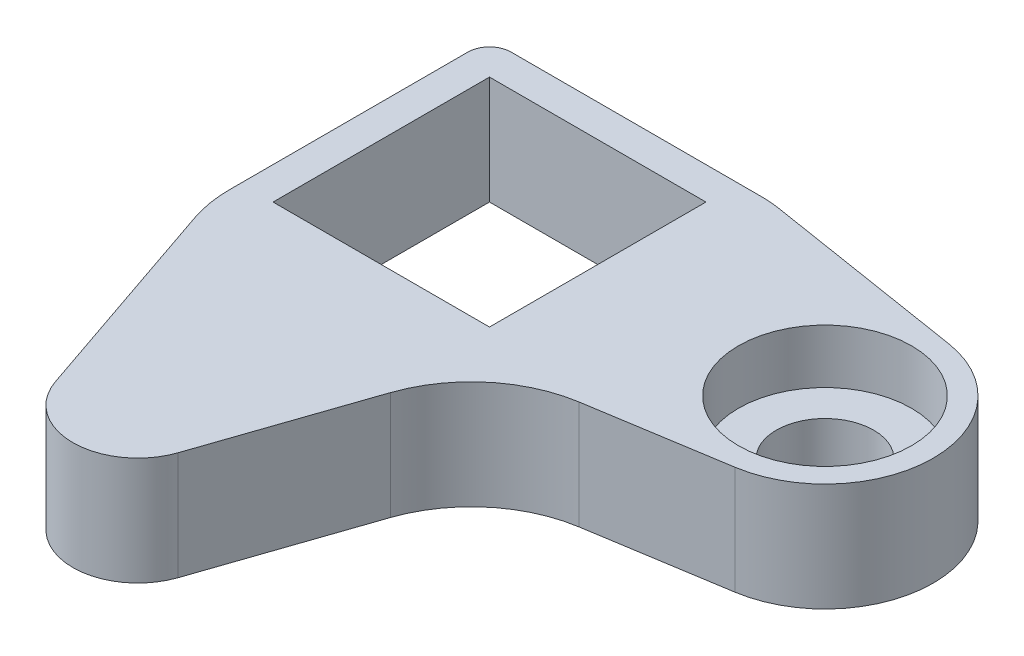
SolidWorks part; units mm, degrees
ref_plane "Front Plane" through (0, 0, 0) normal (0, 0, 1) x (1, 0, 0)
ref_plane "Top Plane" through (0, 0, 0) normal (0, 1, 0) x (1, 0, 0)
ref_plane "Right Plane" through (0, 0, 0) normal (1, 0, 0) x (0, 0, -1)
sketch "Sketch1" plane through (0, 0, 0) normal (0, 1, 0) x (1, 0, 0)
  line L0 (20, 0) -> (41, -10) construction
  line L1 (10, -42.5) -> (0, -20) construction
  line L2 (41, -10) -> (20, -20) construction
  line L3 (0, 0) -> (0, -20) construction
  line L4 (0, 0) -> (20, -20) construction
  line L5 (23.9399, 2.85) -> (42.5764, -0.125)
  line L12 (-3, -23) -> (23, -23) construction
  line L13 (0, 0) -> (20, 0) construction
  line L14 (0, 0) -> (0, -20) construction
  line L15 (0, -20) -> (20, -20) construction
  line L16 (20, 0) -> (20, -20) construction
  line L17 (10, -42.5) -> (20, -20) construction
  line L18 (-3, -21.0074) -> (-3, 1)
  line L19 (-1, 3) -> (22.0482, 3)
  line L20 (23, -23) -> (23, 3) construction
  line L21 (-3, -23) -> (23, 3) construction
  line L22 (-3, 3) -> (23, -23) construction
  line L23 (0, -20) -> (20, -20)
  line L24 (0, -20) -> (0, 0)
  line L25 (0, 0) -> (20, 0)
  line L26 (20, -20) -> (20, 0)
  line L27 (0, -20) -> (20, 0) construction
  line L28 (0, 0) -> (20, -20) construction
  line L29 (30.1306, -21.8617) -> (42.5764, -19.875)
  line L30 (20.6662, -29.8333) -> (15.678, -44.4392)
  line L31 (-2.356, -24.8857) -> (4.322, -44.4392)
  circle A4 centre (10, -42.5) radius 4 construction
  circle A5 centre (41, -10) radius 4 construction
  arc A6 (-3, 1) -> (-1, 3) centre (-1, 1) cw
  circle A7 centre (41, -10) radius 8 construction
  arc A8 (42.5764, -19.875) -> (42.5764, -0.125) centre (41, -10) ccw
  arc A9 (4.322, -44.4392) -> (15.678, -44.4392) centre (10, -42.5) ccw
  arc A10 (30.1306, -21.8617) -> (20.6662, -29.8333) centre (32.0222, -33.7117) ccw
  arc A11 (23.9399, 2.85) -> (22.0482, 3) centre (22.0482, -9) ccw
  arc A12 (-3, -21.0074) -> (-2.356, -24.8857) centre (9, -21.0074) ccw
  point P0 (10, -10)
  point P10 (10, -10)
  dimension "D6" = 8
  dimension "D7" = 16
  dimension "D8" = 20
  dimension "D9" = 12
  dimension "D10" = 12
  dimension "D11" = 12
  dimension "D5" = 2
  dimension "D2" = 20
  dimension "D3" = 3
  dimension "D4" = 42.5
  dimension "D12" = 20
  dimension "D13" = 41
extrude "Boss-Extrude1" add sketch "Sketch1" along normal blind 10
ref_plane "Plane1" through (0, 5, 0) normal (0, 1, 0) x (1, 0, 0)
sketch "Sketch2" plane through (0, 5, 0) normal (0, 1, 0) x (1, 0, 0)
  line L0 (20, 0) -> (41, -10) construction
  line L1 (10, -42.5) -> (0, -20) construction
  line L2 (41, -10) -> (20, -20) construction
  line L3 (0, 0) -> (0, -20) construction
  line L4 (0, 0) -> (20, -20) construction
  line L5 (23.9399, 2.85) -> (42.5764, -0.125) construction
  line L6 (-3, -23) -> (23, -23) construction
  line L7 (0, 0) -> (20, 0) construction
  line L8 (0, 0) -> (0, -20) construction
  line L9 (0, -20) -> (20, -20) construction
  line L10 (20, 0) -> (20, -20) construction
  line L11 (10, -42.5) -> (20, -20) construction
  line L12 (-3, -21.0074) -> (-3, 1) construction
  line L13 (-1, 3) -> (22.0482, 3) construction
  line L14 (23, -23) -> (23, 3) construction
  line L15 (-3, -23) -> (23, 3) construction
  line L16 (-3, 3) -> (23, -23) construction
  line L17 (0, -20) -> (20, -20) construction
  line L18 (0, -20) -> (0, 0) construction
  line L19 (0, 0) -> (20, 0) construction
  line L20 (20, -20) -> (20, 0) construction
  line L21 (0, -20) -> (20, 0) construction
  line L22 (0, 0) -> (20, -20) construction
  line L23 (30.1306, -21.8617) -> (42.5764, -19.875) construction
  line L24 (20.6662, -29.8333) -> (15.678, -44.4392) construction
  line L25 (-2.356, -24.8857) -> (4.322, -44.4392) construction
  circle A0 centre (10, -42.5) radius 4 construction
  circle A1 centre (41, -10) radius 4 construction
  arc A2 (-3, 1) -> (-1, 3) centre (-1, 1) cw construction
  circle A3 centre (41, -10) radius 8
  arc A4 (42.5764, -19.875) -> (42.5764, -0.125) centre (41, -10) ccw construction
  arc A5 (4.322, -44.4392) -> (15.678, -44.4392) centre (10, -42.5) ccw construction
  arc A6 (30.1306, -21.8617) -> (20.6662, -29.8333) centre (32.0222, -33.7117) ccw construction
  arc A7 (23.9399, 2.85) -> (22.0482, 3) centre (22.0482, -9) ccw construction
  arc A8 (-3, -21.0074) -> (-2.356, -24.8857) centre (9, -21.0074) ccw construction
  point P0 (10, -10)
  point P10 (10, -10)
  dimension "D2" = 8
  dimension "D7" = 2
  dimension "D8" = 16
  dimension "D9" = 20
  dimension "D10" = 12
  dimension "D11" = 12
  dimension "D12" = 12
  dimension "D1" = 20
  dimension "D3" = 20
  dimension "D4" = 41
  dimension "D5" = 42.5
  dimension "D6" = 3
extrude "Cut-Extrude2" cut sketch "Sketch2" along normal blind 46
sketch "Sketch3" plane through (0, 5, 0) normal (0, 1, 0) x (1, 0, 0)
  line L0 (20, 0) -> (41, -10) construction
  line L1 (10, -42.5) -> (0, -20) construction
  line L2 (41, -10) -> (20, -20) construction
  line L3 (0, 0) -> (0, -20) construction
  line L4 (0, 0) -> (20, -20) construction
  line L5 (23.9399, 2.85) -> (42.5764, -0.125) construction
  line L6 (-3, -23) -> (23, -23) construction
  line L7 (0, 0) -> (20, 0) construction
  line L8 (0, 0) -> (0, -20) construction
  line L9 (0, -20) -> (20, -20) construction
  line L10 (20, 0) -> (20, -20) construction
  line L11 (10, -42.5) -> (20, -20) construction
  line L12 (-3, -21.0074) -> (-3, 1) construction
  line L13 (-1, 3) -> (22.0482, 3) construction
  line L14 (23, -23) -> (23, 3) construction
  line L15 (-3, -23) -> (23, 3) construction
  line L16 (-3, 3) -> (23, -23) construction
  line L17 (0, -20) -> (20, -20) construction
  line L18 (0, -20) -> (0, 0) construction
  line L19 (0, 0) -> (20, 0) construction
  line L20 (20, -20) -> (20, 0) construction
  line L21 (0, -20) -> (20, 0) construction
  line L22 (0, 0) -> (20, -20) construction
  line L23 (30.1306, -21.8617) -> (42.5764, -19.875) construction
  line L24 (20.6662, -29.8333) -> (15.678, -44.4392) construction
  line L25 (-2.356, -24.8857) -> (4.322, -44.4392) construction
  circle A0 centre (10, -42.5) radius 4
  circle A1 centre (41, -10) radius 4.5
  arc A2 (-3, 1) -> (-1, 3) centre (-1, 1) cw construction
  circle A3 centre (41, -10) radius 8 construction
  arc A4 (42.5764, -19.875) -> (42.5764, -0.125) centre (41, -10) ccw construction
  arc A5 (4.322, -44.4392) -> (15.678, -44.4392) centre (10, -42.5) ccw construction
  arc A6 (30.1306, -21.8617) -> (20.6662, -29.8333) centre (32.0222, -33.7117) ccw construction
  arc A7 (23.9399, 2.85) -> (22.0482, 3) centre (22.0482, -9) ccw construction
  arc A8 (-3, -21.0074) -> (-2.356, -24.8857) centre (9, -21.0074) ccw construction
  point P0 (10, -10)
  point P10 (10, -10)
  dimension "D2" = 8
  dimension "D7" = 2
  dimension "D8" = 16
  dimension "D9" = 20
  dimension "D10" = 12
  dimension "D11" = 12
  dimension "D12" = 12
  dimension "D13" = 9
  dimension "D1" = 20
  dimension "D3" = 20
  dimension "D4" = 41
  dimension "D5" = 42.5
  dimension "D6" = 3
extrude "Cut-Extrude3" cut sketch "Sketch3" against normal blind 10
